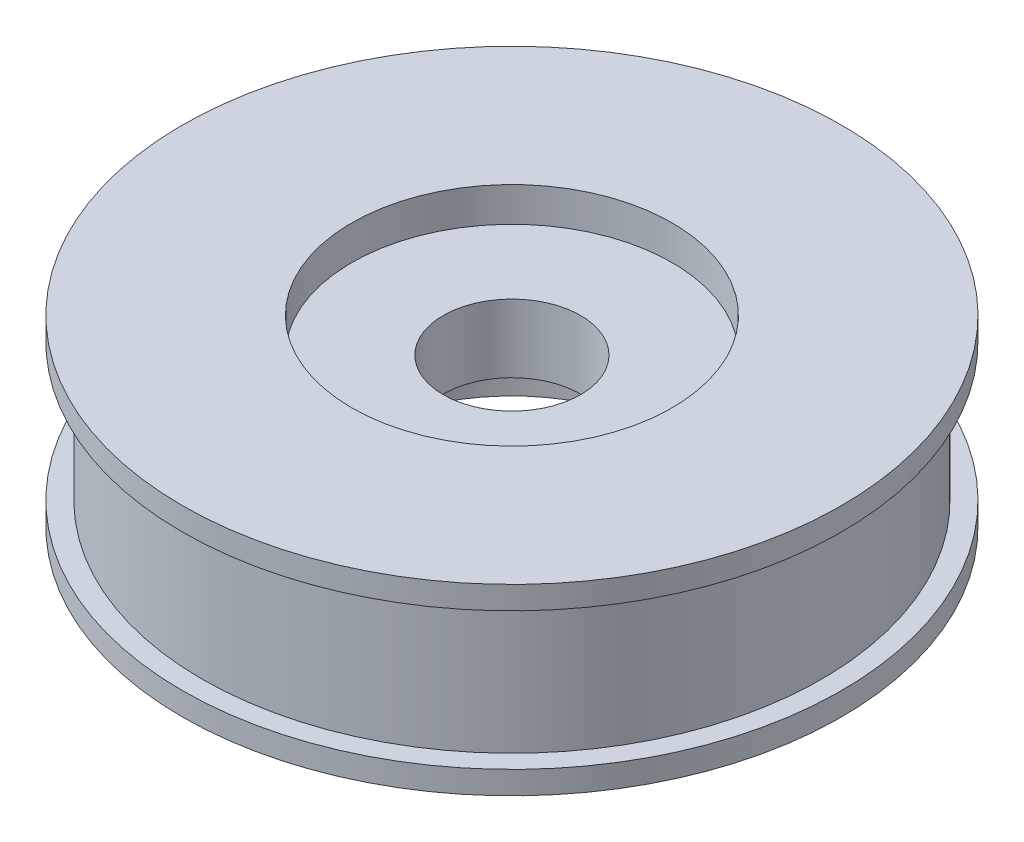
SolidWorks part; units mm, degrees
ref_plane "Front Plane" through (0, 0, 0) normal (0, 0, 1) x (1, 0, 0)
ref_plane "Top Plane" through (0, 0, 0) normal (0, 1, 0) x (1, 0, 0)
ref_plane "Right Plane" through (0, 0, 0) normal (1, 0, 0) x (0, 0, -1)
sketch "Sketch1" plane through (0, 0, 0) normal (0, 1, 0) x (1, 0, 0)
  circle A0 centre (0, 0) radius 22.86
  circle A1 centre (0, 0) radius 11.1125
  dimension "D1" = 45.72
  dimension "D2" = 22.225
extrude "Boss-Extrude1" add sketch "Sketch1" along normal mid plane 12.7
sketch "Sketch3" plane through (0, 0, 0) normal (0, 1, 0) x (1, 0, 0)
  circle A0 centre (0, 0) radius 21.4884
  circle A1 centre (0, 0) radius 22.86
  circle A2 centre (0, 0) radius 22.86 construction
  dimension "D1" = 42.9768
extrude "Cut-Extrude1" cut sketch "Sketch3" along normal offset from surface 1.5875 and the other way offset from surface 1.5875 contours A1 A0 region at (-22.2134, 0, 0) up to face at (0, 6.35, 22.86) other way up to face at (0, -6.35, 22.86)
sketch "Sketch4" plane through (0, 0, 0) normal (0, 1, 0) x (1, 0, 0)
  circle A0 centre (0, 0) radius 11.1125
  circle A1 centre (0, 0) radius 4.7625
  circle A2 centre (0, 0) radius 11.1125 construction
  dimension "D1" = 9.525
extrude "Boss-Extrude5" add sketch "Sketch4" along normal offset from surface 2.3876 and the other way offset from surface 5.588 contours A0 A1 region at (-10.7982, 0, 0) up to face at (0, 6.35, 22.86) other way up to face at (0, -6.35, 22.86)
